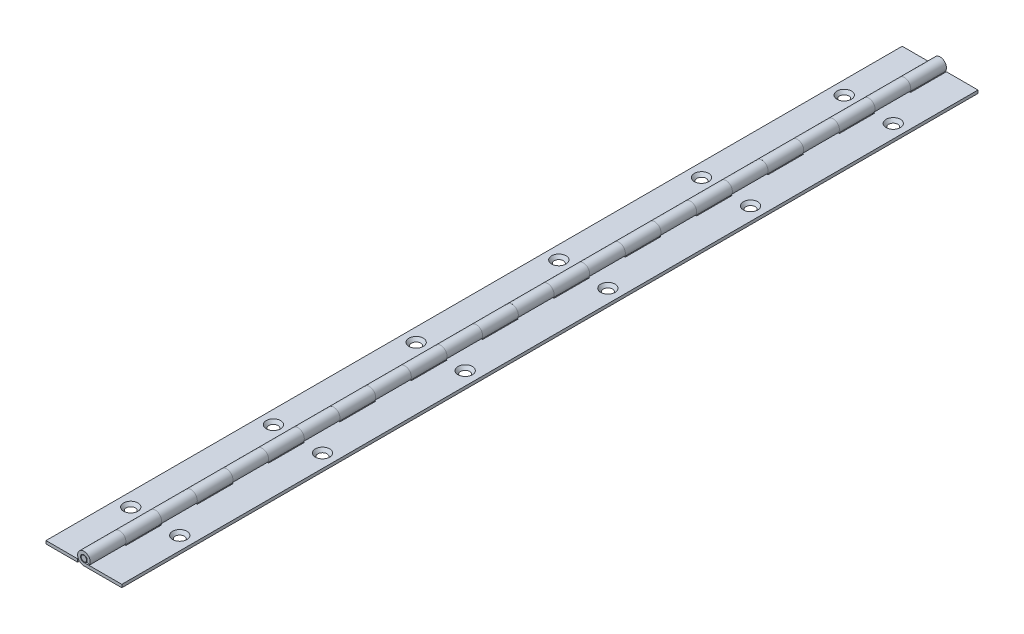
SolidWorks part; units mm, degrees
note: '?' marks a value the reader was unsure of.
ref_plane "Front Plane" through (0, 0, 0) normal (0, 0, 1) x (1, 0, 0)
ref_plane "Top Plane" through (0, 0, 0) normal (0, 1, 0) x (1, 0, 0)
ref_plane "Right Plane" through (0, 0, 0) normal (1, 0, 0) x (0, 0, -1)
sketch "Sketch1" plane through (0, 0, 0) normal (0, 0, 1) x (1, 0, 0)
  line L0 (1.9176, -1.19) -> (13.4937, -1.19)
  line L1 (13.4937, -1.19) -> (13.4937, -2.2568)
  line L2 (13.4937, -2.2568) -> (0, -2.2568)
  line L3 (0, 0) -> (0, 1.1906) construction
  line L4 (-1.1906, 0) -> (-2.2568, 0) construction
  line L5 (1.0791, -0.5032) -> (2.0453, -0.9538) construction
  line L6 (-1.0791, -0.5032) -> (-2.0453, -0.9538) construction
  circle A0 centre (0, 0) radius 1.1906
  circle A1 centre (0, 0) radius 2.2568
  dimension "knuckle dia" = 4.5136
  dimension "leaf thickness" = 1.0668
  dimension "open width" = 26.9875
  dimension "D5" = 25
  dimension "D6" = 25
sketch "Sketch2" plane through (0, 0, 0) normal (0, 0, 1) x (1, 0, 0)
  line L0 (13.4937, -1.19) -> (13.4937, -2.2568) construction
  line L1 (1.9176, -1.19) -> (13.4937, -1.19) construction
  line L2 (1.0791, -0.5032) -> (2.0453, -0.9538) construction
  line L3 (13.4937, -2.2568) -> (0, -2.2568) construction
  line L4 (13.4937, -1.19) -> (13.4937, -2.2568)
  line L5 (-0.0389, -1.19) -> (13.4937, -1.19)
  line L6 (1.0791, -0.5032) -> (2.0453, -0.9538)
  line L7 (13.4937, -2.2568) -> (0, -2.2568)
  circle A0 centre (0, 0) radius 1.1906 construction
  circle A1 centre (0, 0) radius 2.2568 construction
  arc A2 (1.0791, -0.5032) -> (-0.0389, -1.19) centre (0, 0) ccw
  arc A3 (2.0453, -0.9538) -> (0, -2.2568) centre (0, 0) ccw
extrude "Extrude1" add sketch "Sketch2" along normal mid plane 304.8
sketch "Sketch3" plane through (0, -1.19, 0) normal (0, 1, 0) x (1, 0, 0)
  line L1 (-2.2568, 152.4) -> (2.2568, 152.4)
  line L2 (-2.2568, 152.4) -> (-2.2568, 139.7)
  line L3 (-2.2568, 139.7) -> (2.2568, 139.7)
  line L4 (2.2568, 152.4) -> (2.2568, 139.7)
  line L6 (2.2568, 152.4) -> (-2.2568, 152.4) construction
  line L7 (2.2568, -152.4) -> (2.2568, 152.4) construction
  line L8 (-2.2568, 152.4) -> (-2.2568, -152.4) construction
  dimension "knuckle length" = 12.7
extrude "Cut-Extrude1" cut sketch "Sketch3" against normal mid plane 50.8
pattern_linear "LPattern1" count 12 spacing 25.4 along (0, 0, 1) of "Cut-Extrude1"
sketch "Sketch5" plane through (0, 0, -152.4) normal (0, 0, -1) x (-1, 0, 0)
  line L0 (-1.9176, -1.19) -> (-13.4937, -1.19) construction
  line L1 (-13.4937, -2.2568) -> (0, -2.2568) construction
  line L2 (0.0389, -1.19) -> (13.4937, -1.19)
  line L3 (13.4937, -2.2568) -> (0, -2.2568)
  line L4 (1.0791, -0.5032) -> (2.0453, -0.9538) construction
  line L5 (1.0791, -0.5032) -> (2.0453, -0.9538)
  line L6 (13.4937, -1.19) -> (13.4937, -2.2568)
  line L8 (0, 0) -> (0, -2.2568) construction
  circle A0 centre (0, 0) radius 2.2568 construction
  arc A1 (2.0453, -0.9538) -> (0, -2.2568) centre (0, 0) ccw
  circle A2 centre (0, 0) radius 1.1906 construction
  arc A3 (1.0791, -0.5032) -> (0.0389, -1.19) centre (0, 0) ccw
  dimension "D1" = 26.9875
extrude "Extrude2" add sketch "Sketch5" against normal blind 12.7 separate body
pattern_linear "LPattern3" count 12 spacing 25.4 along (0, 0, 1) of bodies 104
sketch "Sketch6" plane through (0, 0, -152.4) normal (0, 0, -1) x (-1, 0, 0)
  line L0 (0, -2.2568) -> (13.4937, -2.2568) construction
  line L1 (13.4937, -1.19) -> (2.2822, -1.19)
  line L2 (13.4937, -1.19) -> (13.4937, -2.2568)
  line L3 (13.4937, -2.2568) -> (2.2822, -2.2568)
  line L4 (2.2822, -1.19) -> (2.2822, -2.2568)
  line L6 (13.4937, -1.19) -> (0.0389, -1.19) construction
  line L7 (2.2568, 1.5054) -> (2.2568, -2.5761) construction
  arc A0 (2.0453, -0.9538) -> (0, -2.2568) centre (0, 0) ccw construction
  dimension "D1" = 0.0254
extrude "Extrude5" add sketch "Sketch6" against normal blind 304.8
sketch "Sketch10" plane through (0, -2.2568, 0) normal (0, 1, 0) x (1, 0, 0)
  line L0 (13.4937, -152.4) -> (13.4937, 152.4) construction
  line L2 (13.4937, 152.4) -> (2.2568, 152.4) construction
  circle A0 centre (8.7312, 127) radius 1.632
  point P2 (7.8753, 152.4)
  dimension "hole dia" = 3.2639
  dimension "A" = 25.4
  dimension "D" = 4.7625
extrude "Cut-Extrude2" cut sketch "Sketch10" along normal up to surface (1.0668 mm away) draft 41
pattern_linear "LPattern4" count 6 spacing 50.8 along (0, 0, 1) of "Cut-Extrude2"
mirror "Mirror3" about plane through (0, 0, 0) normal (1, 0, 0) of "LPattern4", "Cut-Extrude2"
sketch "Sketch7" plane through (0, 0, 0) normal (0, 0, 1) x (1, 0, 0)
  circle A0 centre (0, 0) radius 1.1906 construction
  circle A1 centre (0, 0) radius 1.1906
extrude "Extrude4" add sketch "Sketch7" along normal mid plane 304.8 separate body
chamfer "Chamfer1" distance 0.2381 angle 45 2 edges at (1.1906, 0, 152.4) (1.1906, 0, -152.4)
sketch "Sketch8" plane through (0, 0, 0) normal (0, 1, 0) x (1, 0, 0)
  line L0 (13.4937, 0) -> (-13.4937, 0) construction
  line L1 (13.4937, 0) -> (0, 0) construction
  line L2 (-13.4937, -152.4) -> (-13.4937, 152.4) construction
  line L3 (13.4937, -152.4) -> (13.4937, 152.4) construction
ref_axis "Axis1" through (-13.4937, 0, 0) along (1, 0, 0)?
ref_plane "  " through (0, 0, 0) normal (0, 0.866, 0.5) x (1, 0, 0)
sketch "Sketch9" plane through (0, 0, 0) normal (0, 1, 0) x (1, 0, 0)
  line L0 (2.2568, 139.7) -> (2.2568, 152.4) construction
  point P0 (-13.4937, 152.4)
  point P1 (13.4937, 152.4)
  point P3 (-13.4937, -152.4)
  point P5 (13.4937, -152.4)
  point P7 (2.2568, 139.7)
sketch "Sketch11" plane through (0, 0, 0) normal (0, 0, 1) x (1, 0, 0)
  line L0 (-2.2568, 0) -> (-2.2568, -2.2568)
  line L1 (-2.2568, -2.2568) -> (2.2568, -2.2568)
  line L2 (2.2568, -2.2568) -> (2.2568, 0)
  line L3 (0, -2.2568) -> (13.4937, -2.2568) construction
  circle A0 centre (0, 0) radius 2.2568
  circle A1 centre (0, 0) radius 2.2568 construction
equation "\"D1@LPattern1\" = \"overall length@Extrude1\"/(\"knuckle length@Sketch3\"*2)"
equation "\"D1@Sketch5\" = \"open width@Sketch1\""
equation "\"D1@LPattern3\" = \"D1@LPattern1\""
equation "\"D1@Extrude4\" = \"overall length@Extrude1\""
equation "\"D3@LPattern1\" = \"knuckle length@Sketch3\"*2"
equation "\"D3@LPattern3\" = \"D3@LPattern1\""
equation "\"D1@Chamfer1\" = \"pin diameter@Sketch1\"*.1"
equation "\"D1@Extrude2\" = \"knuckle length@Sketch3\""
equation "\"D1@Extrude5\" = \"overall length@Extrude1\""
equation "\"D1@LPattern4\" = \"overall length@Extrude1\"/2"
